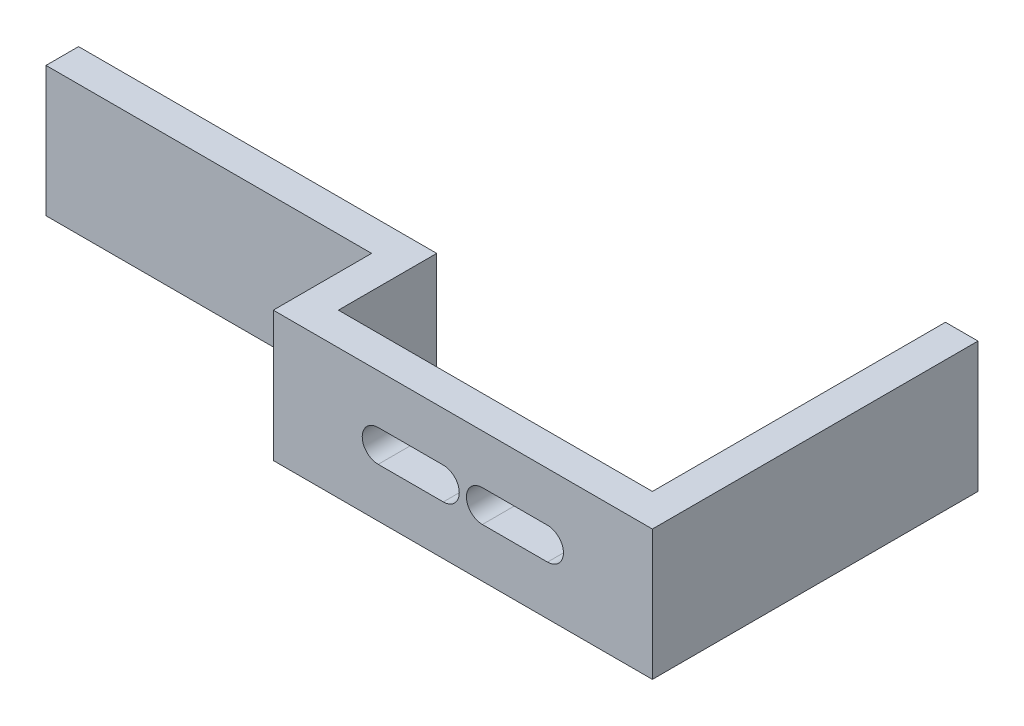
SolidWorks part; units mm, degrees
ref_plane "Front Plane" through (0, 0, 0) normal (0, 0, 1) x (1, 0, 0)
ref_plane "Top Plane" through (0, 0, 0) normal (0, 1, 0) x (1, 0, 0)
ref_plane "Right Plane" through (0, 0, 0) normal (1, 0, 0) x (0, 0, -1)
sketch "Sketch1" plane through (0, 0, 0) normal (0, 1, 0) x (1, 0, 0)
  line L1 (0, 0) -> (36.9697, 0)
  line L2 (0, 0) -> (0, 3.175)
  line L3 (3.175, 3.175) -> (33.7947, 3.175)
  line L4 (36.9697, 0) -> (36.9697, 3.175)
  line L6 (0, 3.175) -> (0, 9.5885)
  line L7 (0, 12.7635) -> (3.175, 12.7635)
  line L8 (3.175, 3.175) -> (3.175, 12.7635)
  line L9 (0, 12.7635) -> (-31.75, 12.7635)
  line L11 (0, 9.5885) -> (-31.75, 9.5885)
  line L12 (-31.75, 12.7635) -> (-31.75, 9.5885)
  line L14 (36.9697, 3.175) -> (36.9697, 31.75)
  line L15 (36.9697, 31.75) -> (33.7947, 31.75)
  line L16 (33.7947, 3.175) -> (33.7947, 31.75)
  point P14 (0, 0)
  dimension "D1" = 3.175
  dimension "D2" = 30.6197
  dimension "D3" = 3.175
  dimension "D4" = 31.75
  dimension "D5" = 9.5885
  dimension "D6" = 3.175
  dimension "D7" = 3.175
  dimension "D8" = 31.75
extrude "Boss-Extrude1" add sketch "Sketch1" along normal blind 12.7
sketch "Sketch2" plane through (0, 0, 0) normal (0, 0, 1) x (1, 0, 0)
  line L0 (10.2298, 6.35) -> (16.5798, 6.35) construction
  line L1 (10.2298, 7.9058) -> (16.5799, 7.9058)
  line L2 (10.2298, 4.7942) -> (16.5799, 4.7942)
  line L3 (0, 12.7) -> (0, 0) construction
  line L4 (18.4848, 12.7) -> (18.4848, 0) construction
  line L5 (0, 12.7) -> (36.9697, 12.7) construction
  line L6 (0, 0) -> (36.9697, 0) construction
  line L7 (26.7398, 6.35) -> (20.3899, 6.35) construction
  line L8 (26.7399, 7.9058) -> (20.3898, 7.9058)
  line L9 (26.7399, 4.7943) -> (20.3898, 4.7942)
  line L10 (13.4048, 6.35) -> (23.5649, 6.35) construction
  arc A0 (10.2298, 7.9058) -> (10.2298, 4.7942) centre (10.2298, 6.35) ccw
  arc A1 (16.5799, 4.7942) -> (16.5799, 7.9058) centre (16.5798, 6.35) ccw
  arc A2 (26.7399, 7.9058) -> (26.7399, 4.7943) centre (26.7398, 6.35) cw
  arc A3 (20.3898, 4.7942) -> (20.3898, 7.9058) centre (20.3899, 6.35) cw
  point P2 (13.4048, 6.35)
  point P9 (0, 6.35)
  point P18 (23.5648, 6.35)
  dimension "D1" = 1.5557
  dimension "D2" = 6.35
  dimension "D3" = 10.16
extrude "Cut-Extrude1" cut sketch "Sketch2" against normal through all
